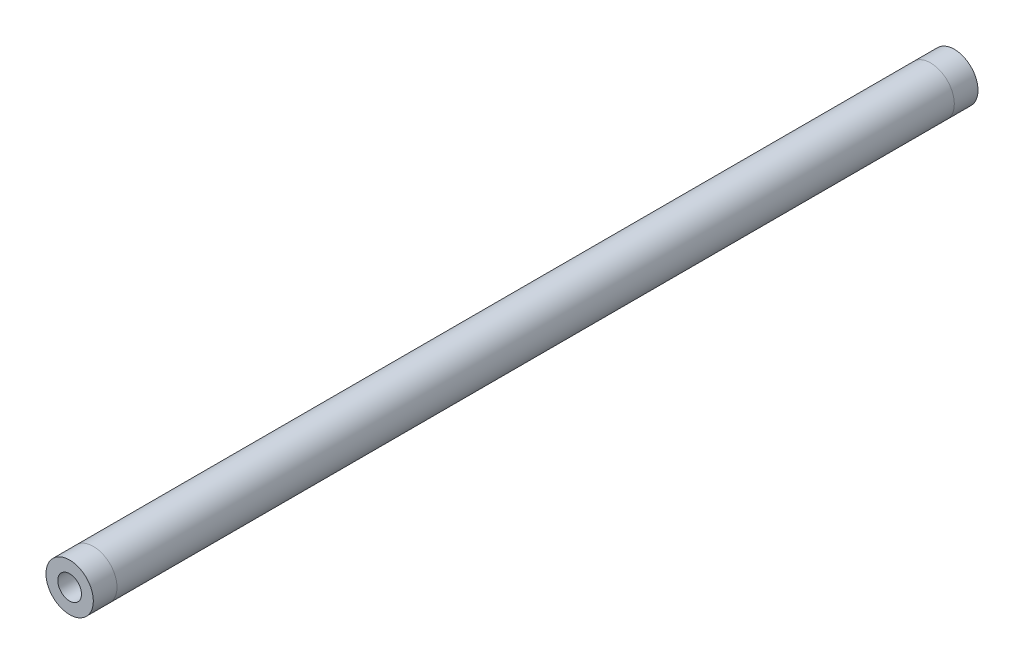
SolidWorks part; units mm, degrees
ref_plane "Front Plane" through (0, 0, 0) normal (0, 0, 1) x (1, 0, 0)
ref_plane "Top Plane" through (0, 0, 0) normal (0, 1, 0) x (1, 0, 0)
ref_plane "Right Plane" through (0, 0, 0) normal (1, 0, 0) x (0, 0, -1)
sketch "Axis" plane through (0, 0, 0) normal (1, 0, 0) x (0, 0, -1)
  line L0 (0, 0) -> (237.2056, 0) construction
  line L1 (237.2056, 0) -> (230.8556, 0)
  line L2 (237.2056, 0) -> (259.1004, 0) construction
  line L3 (0, 0) -> (-21.8948, 0) construction
  point P4 (0, 0)
  point P5 (237.2056, 0)
  point P6 (230.8556, 0)
  dimension "D1" = 6.35
  dimension "D2" = 21.8948
  dimension "D3" = 21.8948
sketch "Sketch1" plane through (0, 0, 0) normal (0, 0, 1) x (1, 0, 0)
  circle A0 centre (0, 0) radius 6.35
  circle A1 centre (0, 0) radius 4.826
  circle A2 centre (0, 0) radius 3.175
  dimension "D1" = 12.7
  dimension "D2" = 1.524
  dimension "D3" = 6.35
extrude "Threaded insert 1-1" add sketch "Sketch1" against normal blind 6.35 contours A0 A1 | A1 A2 region at (-6.1704, 0, 0) region at (-4.6895, 0, 0)
extrude "Threaded insert 1-2" add sketch "Sketch1<3>" against normal blind 9.525 from surface contours A1 A2 region at (-4.6895, 0, 0) starting at face at (6.35, 0, -6.35)
sketch "Sketch1<3>" plane through (0, 0, 0) normal (0, 0, 1) x (1, 0, 0) same geometry as "Sketch1"
extrude "Tube extrude" add sketch "Sketch1<4>" against normal up to vertex (230.8556 mm away) from surface separate body contours A0 A1 region at (-6.1704, 0, 0) up to point (0, 0, -230.8556) starting at face at (4.826, 0, -6.35)
sketch "Sketch1<4>" plane through (0, 0, 0) normal (0, 0, 1) x (1, 0, 0) same geometry as "Sketch1"
extrude "Threaded insert 2-1" add sketch "Sketch1<6>" along normal blind 9.525 from surface separate body contours A1 A2 region at (-4.6895, 0, 0) starting at face at (4.826, 0, -230.8556)
sketch "Sketch1<6>" plane through (0, 0, 0) normal (0, 0, 1) x (1, 0, 0) same geometry as "Sketch1"
extrude "Threaded insert 2-2" add sketch "Sketch1<9>" against normal blind 6.35 from surface separate body contours A1 A2 | A0 A1 region at (-6.1704, 0, 0) region at (-4.6895, 0, 0) starting at face at (4.826, 0, -230.8556)
sketch "Sketch1<9>" plane through (0, 0, 0) normal (0, 0, 1) x (1, 0, 0) same geometry as "Sketch1"
combine bodies "Combine1" operation type add bodies to combine 106 104
equation "\"Threaded insert outer thickness\"= .25"
equation "\"D1@Threaded insert 1-1\"=\"Threaded insert outer thickness\""
equation "\"D1@Threaded insert 2-2\"=\"Threaded insert outer thickness\""
equation "\"D1@Axis\" = \"Threaded insert outer thickness\""
